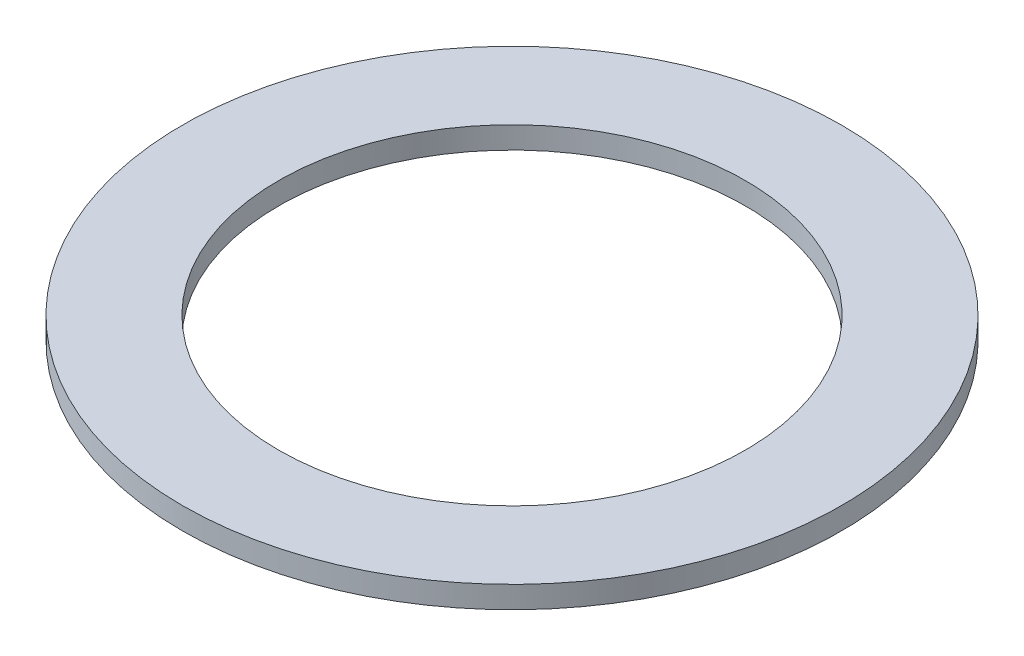
SolidWorks part; units mm, degrees
ref_plane "Front Plane" through (0, 0, 0) normal (0, 0, 1) x (1, 0, 0)
ref_plane "Top Plane" through (0, 0, 0) normal (0, 1, 0) x (1, 0, 0)
ref_plane "Right Plane" through (0, 0, 0) normal (1, 0, 0) x (0, 0, -1)
sketch "Sketch1" plane through (0, 0, 0) normal (0, 1, 0) x (1, 0, 0)
  circle A0 centre (0, 0) radius 60
  dimension "FLANGE_OD" = 120
extrude "Boss-Extrude1" add sketch "Sketch1" along normal blind 4
sketch "Sketch2" plane through (0, 0, 0) normal (0, 1, 0) x (1, 0, 0)
  circle A0 centre (0, 0) radius 42.5
  dimension "BORE_D" = 85
extrude "Cut-Extrude1" cut sketch "Sketch2" along normal through all
sketch "Sketch3" plane through (0, 4, 0) normal (0, 1, 0) x (1, 0, 0)
  circle A0 centre (0, 0) radius 24.565 construction
  circle A1 centre (-24.565, 0) radius 2.9051
  dimension "BOLT_D" = 5.8102
  dimension "BOLT_PCD" = 49.1299
extrude "Cut-Extrude2" cut sketch "Sketch3" against normal blind 3.722 rebuild error yes
pattern_circular "CirPattern1" count 5 over 360 rebuild error yes
